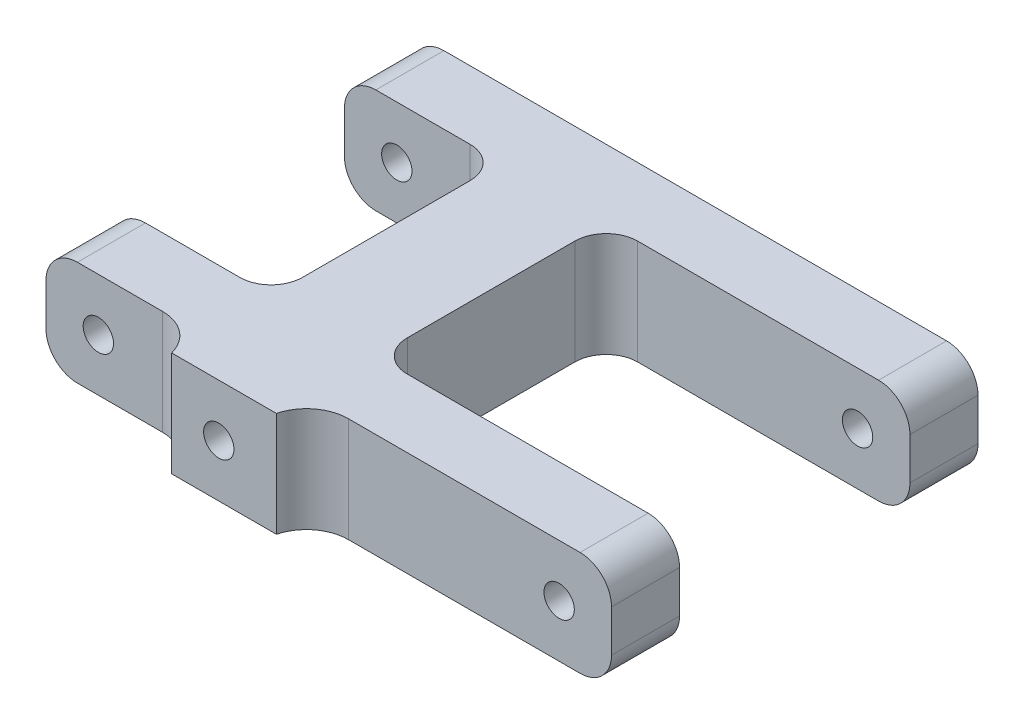
SolidWorks part; units mm, degrees
ref_plane "Front" through (0, 0, 0) normal (0, 0, 1) x (1, 0, 0)
ref_plane "Top" through (0, 0, 0) normal (0, 1, 0) x (1, 0, 0)
ref_plane "Right" through (0, 0, 0) normal (1, 0, 0) x (0, 0, -1)
sketch "Sketch1" plane through (0, 0, 0) normal (0, 1, 0) x (1, 0, 0)
  line L1 (0, 0) -> (54, 0)
  line L2 (0, 0) -> (0, -35)
  line L3 (0, -35) -> (54, -35)
  line L4 (54, 0) -> (54, -35)
  dimension "D1" = 35
  dimension "D2" = 54
extrude "Boss-Extrude1" add sketch "Sketch1" along normal blind 10
sketch "Sketch2" plane through (54, 0, 0) normal (1, 0, 0) x (0, 0, -1)
  line L0 (-35, 10) -> (0, 10) construction
  line L1 (-28.5, 10) -> (-6.5, 10)
  line L2 (-28.5, 10) -> (-28.5, 0)
  line L3 (-28.5, 0) -> (-6.5, 0)
  line L4 (-6.5, 10) -> (-6.5, 0)
  line L5 (-35, 0) -> (0, 0) construction
  line L6 (-35, 10) -> (-35, 0) construction
  line L7 (0, 10) -> (0, 0) construction
  dimension "D1" = 6.5
  dimension "D2" = 6.5
extrude "Cut-Extrude1" cut sketch "Sketch2" against normal blind 29
sketch "Sketch3" plane through (0, 0, 0) normal (-1, 0, 0) x (0, 0, 1)
  line L0 (0, 10) -> (35, 10) construction
  line L1 (6.5, 10) -> (28.5, 10)
  line L2 (6.5, 10) -> (6.5, 0)
  line L3 (6.5, 0) -> (28.5, 0)
  line L4 (28.5, 10) -> (28.5, 0)
  line L5 (0, 0) -> (35, 0) construction
  line L6 (35, 10) -> (35, 0) construction
  line L7 (0, 10) -> (0, 0) construction
  dimension "D1" = 6.5
  dimension "D2" = 6.5
extrude "Cut-Extrude2" cut sketch "Sketch3" against normal blind 15
sketch "Sketch5" plane through (0, 0, 35) normal (0, 0, 1) x (1, 0, 0)
  line L0 (0, 10) -> (54, 10) construction
  line L1 (0, 10) -> (0, 0) construction
  circle A0 centre (5, 5) radius 1.45
  circle A1 centre (49, 5) radius 1.45
  dimension "D1" = 2.9
  dimension "D2" = 5
  dimension "D3" = 5
  dimension "D4" = 2
extrude "Cut-Extrude4" cut sketch "Sketch5" against normal through all
fillet "Fillet1" radius 3 8 edges at (0, 0, 31.75) (0, 10, 31.75) (0, 0, 3.25) (0, 10, 3.25) (54, 10, 3.25) (54, 0, 3.25) (54, 0, 31.75) (54, 10, 31.75)
fillet "Fillet2" radius 3 4 edges at (25, 5, 28.5) (25, 5, 6.5) (15, 5, 28.5) (15, 5, 6.5)
sketch "Sketch8" plane through (0, 0, 35) normal (0, 0, 1) x (1, 0, 0)
  line L0 (3, 10) -> (51, 10) construction
  line L1 (15, 10) -> (25, 10)
  line L2 (15, 10) -> (15, 0)
  line L3 (15, 0) -> (25, 0)
  line L4 (25, 10) -> (25, 0)
  line L5 (3, 0) -> (51, 0) construction
  line L6 (54, 7) -> (54, 3) construction
  line L7 (0, 7) -> (0, 3) construction
  dimension "D1" = 29
  dimension "D2" = 15
extrude "Boss-Extrude2" add sketch "Sketch8" along normal blind 3
sketch "Sketch6" plane through (0, 0, 35) normal (0, 0, 1) x (1, 0, 0)
  line L0 (3, 10) -> (15, 10) construction
  line L2 (54, 7) -> (54, 3) construction
  circle A0 centre (19.5, 5) radius 1.45
  dimension "D1" = 2.9
  dimension "D2" = 5
  dimension "D3" = 34.5
extrude "Cut-Extrude5" cut sketch "Sketch6" against normal blind 15 and the other way blind 4
fillet "Fillet3" radius 4 2 edges at (25, 5, 35) (15, 5, 35)
